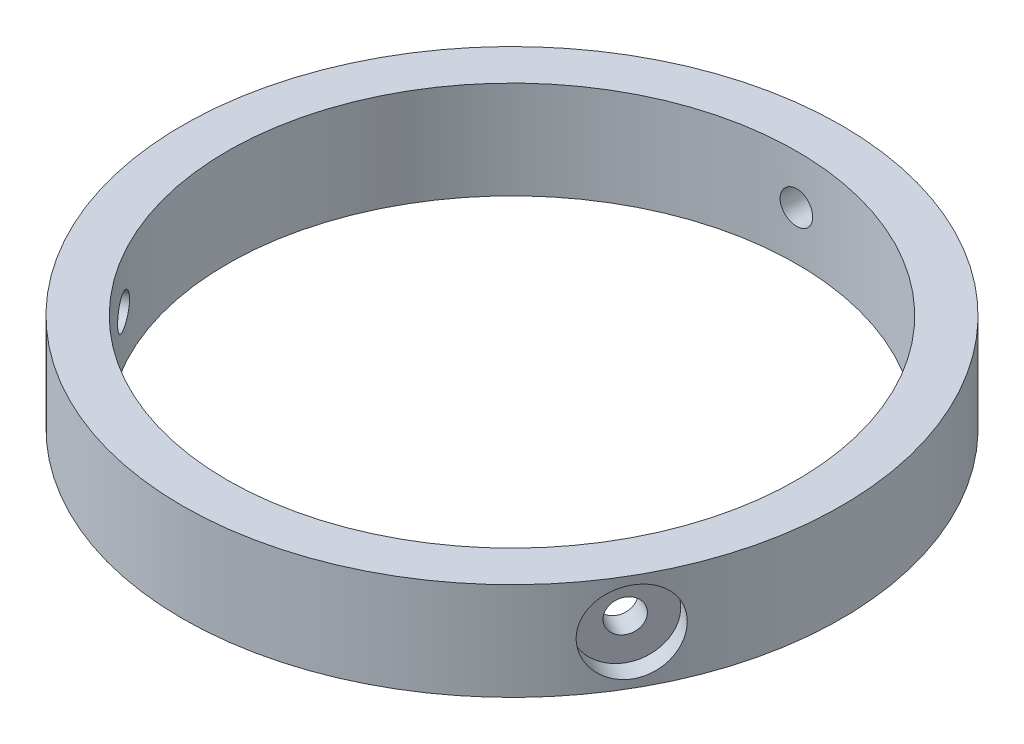
SolidWorks part; units mm, degrees
ref_plane "Front Plane" through (0, 0, 0) normal (0, 0, 1) x (1, 0, 0)
ref_plane "Top Plane" through (0, 0, 0) normal (0, 1, 0) x (1, 0, 0)
ref_plane "Right Plane" through (0, 0, 0) normal (1, 0, 0) x (0, 0, -1)
sketch "Sketch1" plane through (0, 0, 0) normal (0, 1, 0) x (1, 0, 0)
  circle A0 centre (0, 0) radius 17.45
  circle A1 centre (0, 0) radius 12.45
  dimension "D1" = 5
  dimension "D2" = 34.9
extrude "Boss-Extrude1" add sketch "Sketch1" along normal blind 8 and the other way blind 25
sketch "Sketch2" plane through (0, 8, 0) normal (0, 1, 0) x (1, 0, 0)
  circle A0 centre (0, 0) radius 12.45
  circle A1 centre (0, 0) radius 20.25
  dimension "D1" = 40.5
extrude "Boss-Extrude2" add sketch "Sketch2" along normal blind 40
sketch "Sketch3" plane through (0, 48, 0) normal (0, 1, 0) x (1, 0, 0)
  circle A0 centre (0, 0) radius 12.45
  circle A1 centre (0, 0) radius 17.5
  dimension "D1" = 35
extrude "Cut-Extrude1" cut sketch "Sketch3" against normal blind 221
sketch "Sketch4" plane through (0, 0, 0) normal (1, 0, 0) x (0, 0, -1)
  line L0 (-20.25, 8) -> (20.25, 8) construction
  line L1 (39.0407, 115.7728) -> (-39.2593, 115.7728)
  line L2 (39.0407, 115.7728) -> (39.0407, 14)
  line L3 (39.0407, 14) -> (-39.2593, 14)
  line L4 (-39.2593, 115.7728) -> (-39.2593, 14)
  dimension "D1" = 6
extrude "Cut-Extrude2" cut sketch "Sketch4" against normal blind 221 and the other way blind 221
sketch "Sketch5" plane through (0, 0, 0) normal (0, 0, 1) x (1, 0, 0)
  line L0 (20.25, 14) -> (-20.25, 14) construction
  circle A0 centre (0, 11) radius 1
  dimension "D2" = 2
  dimension "D1" = 3
extrude "Cut-Extrude3" cut sketch "Sketch5" against normal blind 221
sketch "Sketch6" plane through (0, 0, 0) normal (0, 0, 1) x (1, 0, 0)
  circle A0 centre (0, 11) radius 2.5
  dimension "D1" = 5
extrude "Cut-Extrude4" cut sketch "Sketch6" against normal blind 221 from offset 19 offset against normal yes
pattern_circular "CirPattern1" count 3 every 120 about axis through (0, 14, 0) along (0, -1, 0) of "Cut-Extrude3", "Cut-Extrude4"
